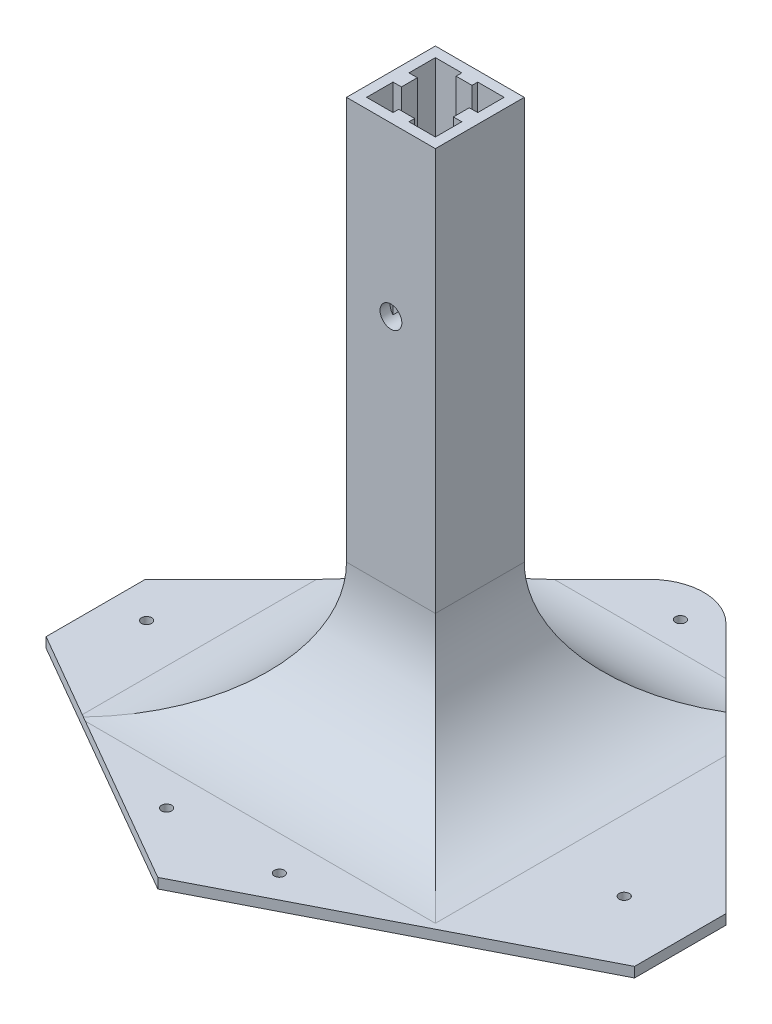
SolidWorks part; units mm, degrees
ref_plane "Alzado" through (0, 0, 0) normal (0, 0, 1) x (1, 0, 0)
ref_plane "Planta" through (0, 0, 0) normal (0, 1, 0) x (1, 0, 0)
ref_plane "Vista lateral" through (0, 0, 0) normal (1, 0, 0) x (0, 0, -1)
sketch "Croquis1" plane through (0, 0, 0) normal (0, 1, 0) x (1, 0, 0)
  line L0 (56.5976, -1117.0407) -> (-18.6736, -1041.7696) construction
  line L1 (56.5976, -1117.0407) -> (56.5976, -1145.3018) construction
  line L2 (56.5976, -1145.3018) -> (-38.4725, -1193.9169) construction
  line L3 (-38.4725, -1193.9169) -> (-118.2589, -1147.8522) construction
  line L4 (-118.2589, -1147.8522) -> (-118.2589, -1117.3133) construction
  line L5 (-42.7152, -1041.7696) -> (-118.2589, -1117.3133) construction
  line L6 (56.5976, -1117.0407) -> (-18.6736, -1041.7696) construction
  line L7 (56.5976, -1117.0407) -> (56.5976, -1145.3018) construction
  line L8 (56.5976, -1145.3018) -> (-38.4725, -1193.9169) construction
  line L9 (-38.4725, -1193.9169) -> (-118.2589, -1147.8522) construction
  line L10 (-118.2589, -1147.8522) -> (-118.2589, -1117.3133) construction
  line L11 (-42.7152, -1041.7696) -> (-118.2589, -1117.3133) construction
  line L24 (-42.0081, -1042.4767) -> (-117.2589, -1117.7275)
  line L25 (-117.2589, -1117.7275) -> (-117.2589, -1147.2748)
  line L26 (-117.2589, -1147.2748) -> (-38.4436, -1192.7789)
  line L27 (-38.4436, -1192.7789) -> (55.5976, -1144.69)
  line L28 (55.5976, -1144.69) -> (55.5976, -1117.4549)
  line L29 (55.5976, -1117.4549) -> (-19.3807, -1042.4767)
  line L30 (-42.0081, -1042.4767) -> (-117.2589, -1117.7275)
  line L31 (-117.2589, -1117.7275) -> (-117.2589, -1147.2748)
  line L32 (-117.2589, -1147.2748) -> (-38.4436, -1192.7789)
  line L33 (-38.4436, -1192.7789) -> (55.5976, -1144.69)
  line L34 (55.5976, -1144.69) -> (55.5976, -1117.4549)
  line L35 (55.5976, -1117.4549) -> (-19.3807, -1042.4767)
  arc A0 (-18.6736, -1041.7696) -> (-42.7152, -1041.7696) centre (-30.6944, -1053.7904) ccw construction
  arc A1 (-18.6736, -1041.7696) -> (-42.7152, -1041.7696) centre (-30.6944, -1053.7904) ccw construction
  arc A4 (-19.3807, -1042.4767) -> (-42.0081, -1042.4767) centre (-30.6944, -1053.7904) ccw
  arc A5 (-19.3807, -1042.4767) -> (-42.0081, -1042.4767) centre (-30.6944, -1053.7904) ccw
  dimension "D1" = 1
extrude "Saliente-Extruir1" add sketch "Croquis1" along normal blind 3
sketch "Croquis2" plane through (0, 3, 0) normal (0, 1, 0) x (1, 0, 0)
  line L0 (-51.7225, -1096.75) -> (-51.7225, -1123.25)
  line L1 (-48.7225, -1099.75) -> (-28.2225, -1099.75)
  line L2 (-48.7225, -1099.75) -> (-48.7225, -1120.25)
  line L3 (-48.7225, -1120.25) -> (-28.2225, -1120.25)
  line L4 (-28.2225, -1099.75) -> (-28.2225, -1120.25)
  line L5 (-48.7225, -1099.75) -> (-28.2225, -1120.25) construction
  line L6 (-48.7225, -1120.25) -> (-28.2225, -1099.75) construction
  line L7 (-51.7225, -1123.25) -> (-25.2225, -1123.25)
  line L8 (-25.2225, -1096.75) -> (-25.2225, -1123.25)
  line L9 (-51.7225, -1096.75) -> (-25.2225, -1096.75)
  line L10 (-38.4725, -1096.75) -> (-38.4725, -1123.25) construction
  circle A0 centre (-38.4725, -1110) radius 5 construction
  circle A1 centre (-38.4725, -1110) radius 5 construction
  dimension "D1" = 20.5
  dimension "D2" = 20.5
  dimension "D3" = 3
extrude "Saliente-Extruir2" add sketch "Croquis2" along normal blind 160
fillet "Redondeo1" radius 40 4 edges at (-38.4725, 3, 1096.75) (-51.7225, 3, 1110) (-25.2225, 3, 1110) (-38.4725, 3, 1123.25)
sketch "Croquis3" plane through (0, 0, 0) normal (0, 1, 0) x (1, 0, 0)
  line L3 (-28.2225, -1120.25) -> (-28.2225, -1099.75)
  line L5 (-28.2225, -1120.25) -> (-28.2225, -1099.75)
  line L7 (-28.2225, -1099.75) -> (-48.7225, -1099.75)
  line L14 (-28.2225, -1099.75) -> (-48.7225, -1099.75)
  line L15 (-48.7225, -1099.75) -> (-48.7225, -1120.25)
  line L16 (-48.7225, -1099.75) -> (-48.7225, -1120.25)
  line L17 (-48.7225, -1120.25) -> (-28.2225, -1120.25)
  line L18 (-48.7225, -1120.25) -> (-28.2225, -1120.25)
  dimension "D1" = 0
extrude "Saliente-Extruir3" add sketch "Croquis3" along normal blind 12
sketch "Croquis5" plane through (0, 12, 0) normal (0, 1, 0) x (1, 0, 0)
  line L0 (-28.2225, -1110) -> (-48.7225, -1110) construction
  line L1 (-28.2225, -1120.25) -> (-28.2225, -1099.75) construction
  line L2 (-48.7225, -1099.75) -> (-48.7225, -1120.25) construction
  line L3 (-38.4725, -1099.75) -> (-38.4725, -1120.25) construction
  line L4 (-28.2225, -1099.75) -> (-48.7225, -1099.75) construction
  line L5 (-48.7225, -1120.25) -> (-28.2225, -1120.25) construction
  circle A0 centre (-38.4725, -1110) radius 4.5
  dimension "D1" = 9
extrude "Cortar-Extruir1" cut sketch "Croquis5" against normal through all both and the other way through all
sketch "Croquis6" plane through (0, 12, 0) normal (0, 1, 0) x (1, 0, 0)
  line L1 (-38.4725, -1102.148) -> (-45.2725, -1106.074)
  line L2 (-45.2725, -1106.074) -> (-45.2725, -1113.926)
  line L3 (-45.2725, -1113.926) -> (-38.4725, -1117.852)
  line L4 (-38.4725, -1117.852) -> (-31.6725, -1113.926)
  line L5 (-31.6725, -1113.926) -> (-31.6725, -1106.074)
  line L6 (-31.6725, -1106.074) -> (-38.4725, -1102.148)
  circle A0 centre (-38.4725, -1110) radius 6.8 construction
  dimension "D1" = 13.6
extrude "Cortar-Extruir2" cut sketch "Croquis6" against normal blind 8
sketch "Croquis7" plane through (0, 12, 0) normal (0, 1, 0) x (1, 0, 0)
  line L0 (-38.4725, -1096.75) -> (-38.4725, -1123.25) construction
  line L1 (-25.2225, -1096.75) -> (-51.7225, -1096.75) construction
  line L2 (-51.7225, -1123.25) -> (-25.2225, -1123.25) construction
  line L3 (-51.7225, -1110) -> (-25.2225, -1110) construction
  line L4 (-51.7225, -1096.75) -> (-51.7225, -1123.25) construction
  line L5 (-25.2225, -1123.25) -> (-25.2225, -1096.75) construction
  line L6 (-40.8475, -1099.75) -> (-40.8475, -1101.45)
  line L7 (-28.2225, -1099.75) -> (-48.7225, -1099.75) construction
  line L8 (-40.8475, -1101.45) -> (-36.0975, -1101.45)
  line L9 (-48.7225, -1107.625) -> (-46.2225, -1107.625)
  line L10 (-48.7225, -1099.75) -> (-48.7225, -1120.25) construction
  line L11 (-46.2225, -1107.625) -> (-46.2225, -1112.375)
  line L12 (-36.0975, -1099.75) -> (-36.0975, -1101.45)
  line L13 (-48.7225, -1112.375) -> (-46.2225, -1112.375)
  line L14 (-36.0975, -1120.25) -> (-36.0975, -1118.55)
  line L15 (-40.8475, -1118.55) -> (-36.0975, -1118.55)
  line L16 (-40.8475, -1120.25) -> (-40.8475, -1118.55)
  line L17 (-28.2225, -1112.375) -> (-30.7225, -1112.375)
  line L18 (-30.7225, -1107.625) -> (-30.7225, -1112.375)
  line L19 (-28.2225, -1107.625) -> (-30.7225, -1107.625)
  line L20 (-40.8475, -1120.25) -> (-36.0975, -1120.25)
  line L21 (-48.7225, -1107.625) -> (-48.7225, -1112.375)
  line L22 (-40.8475, -1099.75) -> (-36.0975, -1099.75)
  line L23 (-28.2225, -1107.625) -> (-28.2225, -1112.375)
  point P23 (-38.4725, -1101.45)
  point P25 (-46.2225, -1110)
  dimension "D1" = 1.7
  dimension "D2" = 2.5
  dimension "D3" = 4.75
  dimension "D4" = 4.75
extrude "Saliente-Extruir4" add sketch "Croquis7" along normal up to surface (151 mm away) up to face at (-38.4725, 163, 1110)
sketch "Croquis8" plane through (0, 0, 1123.25) normal (0, 0, 1) x (1, 0, 0)
  line L0 (-38.4725, 163) -> (-38.4725, 115.0276) construction
  line L1 (-51.7225, 163) -> (-25.2225, 163) construction
  circle A0 centre (-38.4725, 113) radius 3.25
  dimension "D1" = 6.5
  dimension "D2" = 50
extrude "Cortar-Extruir4" cut sketch "Croquis8" against normal through all both and the other way through all
sketch "Croquis9" plane through (0, 3, 0) normal (0, 1, 0) x (1, 0, 0)
  circle A5 centre (-27.0907, -1048.333) radius 1.5
  circle A6 centre (-106.4285, -1128.1413) radius 1.5
  circle A7 centre (-55.0376, -1173.573) radius 1.5
  circle A8 centre (-21.4127, -1173.573) radius 1.5
  circle A9 centre (35.9662, -1128.1413) radius 1.5
extrude "Cortar-Extruir5" cut sketch "Croquis9" against normal through all
